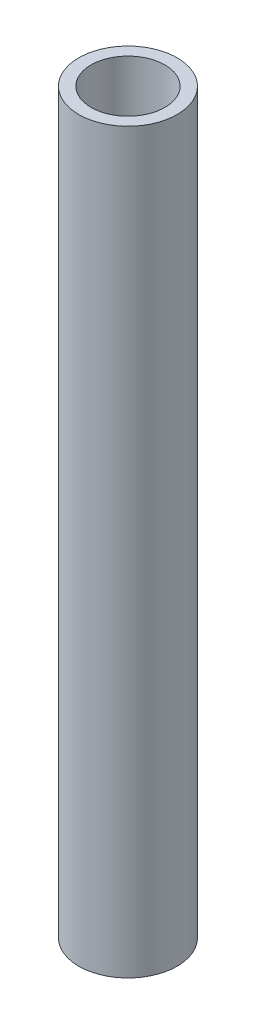
SolidWorks part; units mm, degrees
ref_plane "Front Plane" through (0, 0, 0) normal (0, 0, 1) x (1, 0, 0)
ref_plane "Top Plane" through (0, 0, 0) normal (0, 1, 0) x (1, 0, 0)
ref_plane "Right Plane" through (0, 0, 0) normal (1, 0, 0) x (0, 0, -1)
sketch "Sketch1" plane through (0, 0, 0) normal (0, 1, 0) x (1, 0, 0)
  circle A0 centre (0, 0) radius 4
  dimension "D1" = 8
extrude "Boss-Extrude1" add sketch "Sketch1" along normal blind 60
ref_plane "Plane1" through (0, 25, 0) normal (0, 1, 0) x (1, 0, 0)
sketch "Sketch2" plane through (0, 25, 0) normal (0, 1, 0) x (1, 0, 0)
  circle A2 centre (0, 0) radius 3
  circle A3 centre (0, 0) radius 3
  dimension "D1" = 1
extrude "Cut-Extrude1" cut sketch "Sketch2" along normal through all
sketch "Sketch3" plane through (0, 0, 0) normal (1, 0, 0) x (0, 0, -1)
  line L7 (0, 27.5) -> (0, 31) construction
  line L8 (-2.5, 27.5) -> (-2.5, 31)
  line L9 (2.5, 27.5) -> (2.5, 31)
  line L10 (4.4, 25) -> (-4.4, 25) construction
  line L11 (-4, 60) -> (-4, 0) construction
  arc A0 (-2.5, 27.5) -> (2.5, 27.5) centre (0, 27.5) ccw
  arc A1 (2.5, 31) -> (-2.5, 31) centre (0, 31) ccw
  point P2 (0, 29.25)
  dimension "D2" = 6
  dimension "D4" = 3.5
  dimension "D1" = 1.5
  dimension "D3" = 5
extrude "Cut-Extrude2" cut sketch "Sketch3" against normal through all
sketch "Sketch4" plane through (0, 25, 0) normal (0, 1, 0) x (1, 0, 0)
  circle A2 centre (0, 0) radius 3
  circle A3 centre (0, 0) radius 3
  dimension "D1" = 0
curve "Helix/Spiral1" pitch 100 height 100 turns 1
sketch "Sketch5" plane through (0, 25, 0) normal (0, 1, 0) x (1, 0, 0)
  line L0 (0.7765, 2.8978) -> (0.8541, 3.1876)
  line L1 (-0.7765, 2.8978) -> (-0.8541, 3.1876)
  line L2 (0, 0) -> (4.6731, 0) construction
  line L3 (0, 0) -> (0, 4.6971) construction
  line L4 (2.9959, 0.157) -> (3.2955, 0.1727)
  line L5 (2.516, 1.6339) -> (2.7676, 1.7973)
  line L6 (1.0751, -2.8007) -> (1.1826, -3.0808)
  line L7 (2.3314, -1.888) -> (2.5646, -2.0768)
  line L8 (-2.3314, -1.888) -> (-2.5646, -2.0768)
  line L9 (-1.0751, -2.8007) -> (-1.1826, -3.0808)
  line L10 (-2.516, 1.6339) -> (-2.7676, 1.7973)
  line L11 (-2.9959, 0.157) -> (-3.2955, 0.1727)
  arc A0 (0.8541, 3.1876) -> (-0.8541, 3.1876) centre (0, 0) ccw
  circle A2 centre (0, 0) radius 3
  arc A3 (0.7765, 2.8978) -> (-0.7765, 2.8978) centre (0, 0) ccw
  arc A4 (3.2955, 0.1727) -> (2.7676, 1.7973) centre (0, 0) ccw
  arc A5 (2.9959, 0.157) -> (2.516, 1.6339) centre (0, 0) ccw
  arc A6 (1.1826, -3.0808) -> (2.5646, -2.0768) centre (0, 0) ccw
  arc A7 (1.0751, -2.8007) -> (2.3314, -1.888) centre (0, 0) ccw
  arc A8 (-2.5646, -2.0768) -> (-1.1826, -3.0808) centre (0, 0) ccw
  arc A9 (-2.3314, -1.888) -> (-1.0751, -2.8007) centre (0, 0) ccw
  arc A10 (-2.7676, 1.7973) -> (-3.2955, 0.1727) centre (0, 0) ccw
  arc A11 (-2.516, 1.6339) -> (-2.9959, 0.157) centre (0, 0) ccw
  point P6 (2.7733, 0.8479)
  point P7 (3.3, 0)
  point P31 (0, 0)
  dimension "D3" = 30
  dimension "D4" = 75
  dimension "D1" = 0
  dimension "D2" = 5
sweep "Cut-Sweep1" [suppressed] cut profiles "Sketch5" path "Helix/Spiral1"
sketch "Sketch7" plane through (0, 0, 0) normal (0, 1, 0) x (1, 0, 0)
  circle A0 centre (0, 0) radius 2.7
  dimension "D1" = 5.4
extrude "Cut-Extrude3" cut sketch "Sketch7" along normal up to next
